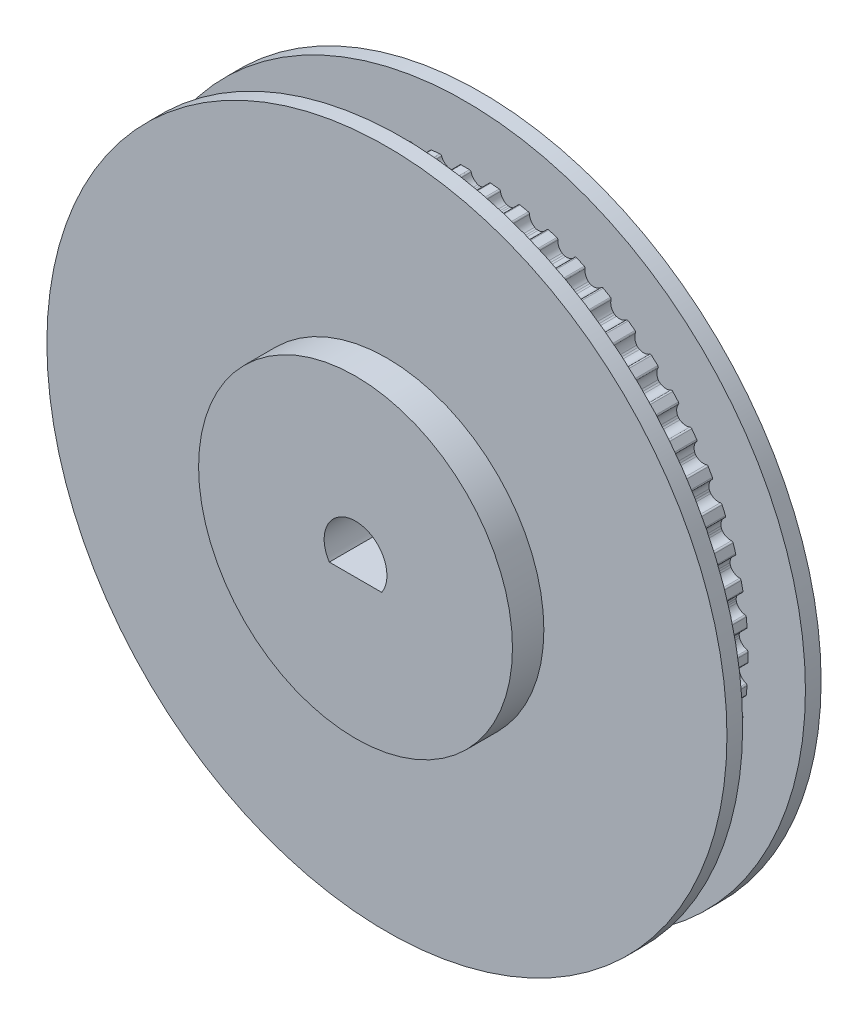
SolidWorks part; units mm, degrees
ref_plane "Front Plane" through (0, 0, 0) normal (0, 0, 1) x (1, 0, 0)
ref_plane "Top Plane" through (0, 0, 0) normal (0, 1, 0) x (1, 0, 0)
ref_plane "Right Plane" through (0, 0, 0) normal (1, 0, 0) x (0, 0, -1)
sketch "Sketch2" plane through (0, 0, 0) normal (0, 0, 1) x (1, 0, 0)
  circle A0 centre (0, 0) radius 27.695
  dimension "D1" = 55.39
extrude "Boss-Extrude1" add sketch "Sketch2" along normal mid plane 6
sketch "Sketch3" plane through (0, 0, 3) normal (0, 0, 1) x (1, 0, 0)
  line L0 (0, 0) -> (0, 27.0327) construction
  line L1 (0, 27.0327) -> (0.4, 27.0327)
  line L4 (0, 0) -> (1.4605, 27.8689) construction
  line L8 (0, 27.0327) -> (0, 27.8689)
  line L9 (0, 27.8689) -> (1.4605, 27.8689)
  line L10 (2.9131, 27.7163) -> (1.4605, 27.8689)
  line L11 (2.8257, 26.8846) -> (2.4279, 26.9264)
  line L12 (2.8257, 26.8846) -> (2.9131, 27.7163)
  line L13 (5.7943, 27.2599) -> (4.3656, 27.5636)
  line L14 (2.9131, 27.7163) -> (4.3656, 27.5636)
  line L15 (2.8257, 26.8846) -> (2.9131, 27.7163)
  line L16 (2.8257, 26.8846) -> (3.2235, 26.8428)
  line L17 (5.6204, 26.442) -> (5.2292, 26.5251)
  line L18 (5.6204, 26.442) -> (5.7943, 27.2599)
  line L19 (8.612, 26.5049) -> (7.2229, 26.9563)
  line L20 (5.7943, 27.2599) -> (7.2229, 26.9563)
  line L21 (5.6204, 26.442) -> (5.7943, 27.2599)
  line L22 (5.6204, 26.442) -> (6.0117, 26.3588)
  line L23 (8.3536, 25.7096) -> (7.9731, 25.8332)
  line L24 (8.3536, 25.7096) -> (8.612, 26.5049)
  line L25 (11.3353, 25.4595) -> (10.001, 26.0536)
  line L26 (8.612, 26.5049) -> (10.001, 26.0536)
  line L27 (8.3536, 25.7096) -> (8.612, 26.5049)
  line L28 (8.3536, 25.7096) -> (8.734, 25.586)
  line L29 (10.9952, 24.6956) -> (10.6298, 24.8583)
  line L30 (10.9952, 24.6956) -> (11.3353, 25.4595)
  line L31 (13.9345, 24.1352) -> (12.6696, 24.8655)
  line L32 (11.3353, 25.4595) -> (12.6696, 24.8655)
  line L33 (10.9952, 24.6956) -> (11.3353, 25.4595)
  line L34 (10.9952, 24.6956) -> (11.3606, 24.5329)
  line L35 (13.5164, 23.411) -> (13.1699, 23.611)
  line L36 (13.5164, 23.411) -> (13.9345, 24.1352)
  line L37 (16.381, 22.5465) -> (15.1993, 23.4049)
  line L38 (13.9345, 24.1352) -> (15.1993, 23.4049)
  line L39 (13.5164, 23.411) -> (13.9345, 24.1352)
  line L40 (13.5164, 23.411) -> (13.8628, 23.211)
  line L41 (15.8894, 21.8699) -> (15.5658, 22.105)
  line L42 (15.8894, 21.8699) -> (16.381, 22.5465)
  line L43 (18.648, 20.7107) -> (17.5626, 21.688)
  line L44 (16.381, 22.5465) -> (17.5626, 21.688)
  line L45 (15.8894, 21.8699) -> (16.381, 22.5465)
  line L46 (15.8894, 21.8699) -> (16.213, 21.6348)
  line L47 (18.0884, 20.0892) -> (17.7911, 20.3569)
  line L48 (18.0884, 20.0892) -> (18.648, 20.7107)
  line L49 (20.7107, 18.648) -> (19.7334, 19.7334)
  line L50 (18.648, 20.7107) -> (19.7334, 19.7334)
  line L51 (18.0884, 20.0892) -> (18.648, 20.7107)
  line L52 (18.0884, 20.0892) -> (18.3857, 19.8216)
  line L53 (20.0892, 18.0884) -> (19.8216, 18.3857)
  line L54 (20.0892, 18.0884) -> (20.7107, 18.648)
  line L55 (22.5465, 16.381) -> (21.688, 17.5626)
  line L56 (20.7107, 18.648) -> (21.688, 17.5626)
  line L57 (20.0892, 18.0884) -> (20.7107, 18.648)
  line L58 (20.0892, 18.0884) -> (20.3569, 17.7911)
  line L59 (21.8699, 15.8894) -> (21.6348, 16.213)
  line L60 (21.8699, 15.8894) -> (22.5465, 16.381)
  line L61 (24.1352, 13.9345) -> (23.4049, 15.1993)
  line L62 (22.5465, 16.381) -> (23.4049, 15.1993)
  line L63 (21.8699, 15.8894) -> (22.5465, 16.381)
  line L64 (21.8699, 15.8894) -> (22.105, 15.5658)
  line L65 (23.411, 13.5164) -> (23.211, 13.8628)
  line L66 (23.411, 13.5164) -> (24.1352, 13.9345)
  line L67 (25.4595, 11.3353) -> (24.8655, 12.6696)
  line L68 (24.1352, 13.9345) -> (24.8655, 12.6696)
  line L69 (23.411, 13.5164) -> (24.1352, 13.9345)
  line L70 (23.411, 13.5164) -> (23.611, 13.1699)
  line L71 (24.6956, 10.9952) -> (24.5329, 11.3606)
  line L72 (24.6956, 10.9952) -> (25.4595, 11.3353)
  line L73 (26.5049, 8.612) -> (26.0536, 10.001)
  line L74 (25.4595, 11.3353) -> (26.0536, 10.001)
  line L75 (24.6956, 10.9952) -> (25.4595, 11.3353)
  line L76 (24.6956, 10.9952) -> (24.8583, 10.6298)
  line L77 (25.7096, 8.3536) -> (25.586, 8.734)
  line L78 (25.7096, 8.3536) -> (26.5049, 8.612)
  line L79 (27.2599, 5.7943) -> (26.9563, 7.2229)
  line L80 (26.5049, 8.612) -> (26.9563, 7.2229)
  line L81 (25.7096, 8.3536) -> (26.5049, 8.612)
  line L82 (25.7096, 8.3536) -> (25.8332, 7.9731)
  line L83 (26.442, 5.6204) -> (26.3588, 6.0117)
  line L84 (26.442, 5.6204) -> (27.2599, 5.7943)
  line L85 (27.7163, 2.9131) -> (27.5636, 4.3656)
  line L86 (27.2599, 5.7943) -> (27.5636, 4.3656)
  line L87 (26.442, 5.6204) -> (27.2599, 5.7943)
  line L88 (26.442, 5.6204) -> (26.5251, 5.2292)
  line L89 (26.8846, 2.8257) -> (26.8428, 3.2235)
  line L90 (26.8846, 2.8257) -> (27.7163, 2.9131)
  line L91 (27.8689, 0) -> (27.8689, 1.4605)
  line L92 (27.7163, 2.9131) -> (27.8689, 1.4605)
  line L93 (26.8846, 2.8257) -> (27.7163, 2.9131)
  line L94 (26.8846, 2.8257) -> (26.9264, 2.4279)
  line L95 (27.0327, 0) -> (27.0327, 0.4)
  line L96 (27.0327, 0) -> (27.8689, 0)
  line L97 (27.7163, -2.9131) -> (27.8689, -1.4605)
  line L98 (27.8689, 0) -> (27.8689, -1.4605)
  line L99 (27.0327, 0) -> (27.8689, 0)
  line L100 (27.0327, 0) -> (27.0327, -0.4)
  line L101 (26.8846, -2.8257) -> (26.9264, -2.4279)
  line L102 (26.8846, -2.8257) -> (27.7163, -2.9131)
  line L103 (27.2599, -5.7943) -> (27.5636, -4.3656)
  line L104 (27.7163, -2.9131) -> (27.5636, -4.3656)
  line L105 (26.8846, -2.8257) -> (27.7163, -2.9131)
  line L106 (26.8846, -2.8257) -> (26.8428, -3.2235)
  line L107 (26.442, -5.6204) -> (26.5251, -5.2292)
  line L108 (26.442, -5.6204) -> (27.2599, -5.7943)
  line L109 (26.5049, -8.612) -> (26.9563, -7.2229)
  line L110 (27.2599, -5.7943) -> (26.9563, -7.2229)
  line L111 (26.442, -5.6204) -> (27.2599, -5.7943)
  line L112 (26.442, -5.6204) -> (26.3588, -6.0117)
  line L113 (25.7096, -8.3536) -> (25.8332, -7.9731)
  line L114 (25.7096, -8.3536) -> (26.5049, -8.612)
  line L115 (25.4595, -11.3353) -> (26.0536, -10.001)
  line L116 (26.5049, -8.612) -> (26.0536, -10.001)
  line L117 (25.7096, -8.3536) -> (26.5049, -8.612)
  line L118 (25.7096, -8.3536) -> (25.586, -8.734)
  line L119 (24.6956, -10.9952) -> (24.8583, -10.6298)
  line L120 (24.6956, -10.9952) -> (25.4595, -11.3353)
  line L121 (24.1352, -13.9345) -> (24.8655, -12.6696)
  line L122 (25.4595, -11.3353) -> (24.8655, -12.6696)
  line L123 (24.6956, -10.9952) -> (25.4595, -11.3353)
  line L124 (24.6956, -10.9952) -> (24.5329, -11.3606)
  line L125 (23.411, -13.5164) -> (23.611, -13.1699)
  line L126 (23.411, -13.5164) -> (24.1352, -13.9345)
  line L127 (22.5465, -16.381) -> (23.4049, -15.1993)
  line L128 (24.1352, -13.9345) -> (23.4049, -15.1993)
  line L129 (23.411, -13.5164) -> (24.1352, -13.9345)
  line L130 (23.411, -13.5164) -> (23.211, -13.8628)
  line L131 (21.8699, -15.8894) -> (22.105, -15.5658)
  line L132 (21.8699, -15.8894) -> (22.5465, -16.381)
  line L133 (20.7107, -18.648) -> (21.688, -17.5626)
  line L134 (22.5465, -16.381) -> (21.688, -17.5626)
  line L135 (21.8699, -15.8894) -> (22.5465, -16.381)
  line L136 (21.8699, -15.8894) -> (21.6348, -16.213)
  line L137 (20.0892, -18.0884) -> (20.3569, -17.7911)
  line L138 (20.0892, -18.0884) -> (20.7107, -18.648)
  line L139 (18.648, -20.7107) -> (19.7334, -19.7334)
  line L140 (20.7107, -18.648) -> (19.7334, -19.7334)
  line L141 (20.0892, -18.0884) -> (20.7107, -18.648)
  line L142 (20.0892, -18.0884) -> (19.8216, -18.3857)
  line L143 (18.0884, -20.0892) -> (18.3857, -19.8216)
  line L144 (18.0884, -20.0892) -> (18.648, -20.7107)
  line L145 (16.381, -22.5465) -> (17.5626, -21.688)
  line L146 (18.648, -20.7107) -> (17.5626, -21.688)
  line L147 (18.0884, -20.0892) -> (18.648, -20.7107)
  line L148 (18.0884, -20.0892) -> (17.7911, -20.3569)
  line L149 (15.8894, -21.8699) -> (16.213, -21.6348)
  line L150 (15.8894, -21.8699) -> (16.381, -22.5465)
  line L151 (13.9345, -24.1352) -> (15.1993, -23.4049)
  line L152 (16.381, -22.5465) -> (15.1993, -23.4049)
  line L153 (15.8894, -21.8699) -> (16.381, -22.5465)
  line L154 (15.8894, -21.8699) -> (15.5658, -22.105)
  line L155 (13.5164, -23.411) -> (13.8628, -23.211)
  line L156 (13.5164, -23.411) -> (13.9345, -24.1352)
  line L157 (11.3353, -25.4595) -> (12.6696, -24.8655)
  line L158 (13.9345, -24.1352) -> (12.6696, -24.8655)
  line L159 (13.5164, -23.411) -> (13.9345, -24.1352)
  line L160 (13.5164, -23.411) -> (13.1699, -23.611)
  line L161 (10.9952, -24.6956) -> (11.3606, -24.5329)
  line L162 (10.9952, -24.6956) -> (11.3353, -25.4595)
  line L163 (8.612, -26.5049) -> (10.001, -26.0536)
  line L164 (11.3353, -25.4595) -> (10.001, -26.0536)
  line L165 (10.9952, -24.6956) -> (11.3353, -25.4595)
  line L166 (10.9952, -24.6956) -> (10.6298, -24.8583)
  line L167 (8.3536, -25.7096) -> (8.734, -25.586)
  line L168 (8.3536, -25.7096) -> (8.612, -26.5049)
  line L169 (5.7943, -27.2599) -> (7.2229, -26.9563)
  line L170 (8.612, -26.5049) -> (7.2229, -26.9563)
  line L171 (8.3536, -25.7096) -> (8.612, -26.5049)
  line L172 (8.3536, -25.7096) -> (7.9731, -25.8332)
  line L173 (5.6204, -26.442) -> (6.0117, -26.3588)
  line L174 (5.6204, -26.442) -> (5.7943, -27.2599)
  line L175 (2.9131, -27.7163) -> (4.3656, -27.5636)
  line L176 (5.7943, -27.2599) -> (4.3656, -27.5636)
  line L177 (5.6204, -26.442) -> (5.7943, -27.2599)
  line L178 (5.6204, -26.442) -> (5.2292, -26.5251)
  line L179 (2.8257, -26.8846) -> (3.2235, -26.8428)
  line L180 (2.8257, -26.8846) -> (2.9131, -27.7163)
  line L181 (0, -27.8689) -> (1.4605, -27.8689)
  line L182 (2.9131, -27.7163) -> (1.4605, -27.8689)
  line L183 (2.8257, -26.8846) -> (2.9131, -27.7163)
  line L184 (2.8257, -26.8846) -> (2.4279, -26.9264)
  line L185 (0, -27.0327) -> (0.4, -27.0327)
  line L186 (0, -27.0327) -> (0, -27.8689)
  line L187 (-2.9131, -27.7163) -> (-1.4605, -27.8689)
  line L188 (0, -27.8689) -> (-1.4605, -27.8689)
  line L189 (0, -27.0327) -> (0, -27.8689)
  line L190 (0, -27.0327) -> (-0.4, -27.0327)
  line L191 (-2.8257, -26.8846) -> (-2.4279, -26.9264)
  line L192 (-2.8257, -26.8846) -> (-2.9131, -27.7163)
  line L193 (-5.7943, -27.2599) -> (-4.3656, -27.5636)
  line L194 (-2.9131, -27.7163) -> (-4.3656, -27.5636)
  line L195 (-2.8257, -26.8846) -> (-2.9131, -27.7163)
  line L196 (-2.8257, -26.8846) -> (-3.2235, -26.8428)
  line L197 (-5.6204, -26.442) -> (-5.2292, -26.5251)
  line L198 (-5.6204, -26.442) -> (-5.7943, -27.2599)
  line L199 (-8.612, -26.5049) -> (-7.2229, -26.9563)
  line L200 (-5.7943, -27.2599) -> (-7.2229, -26.9563)
  line L201 (-5.6204, -26.442) -> (-5.7943, -27.2599)
  line L202 (-5.6204, -26.442) -> (-6.0117, -26.3588)
  line L203 (-8.3536, -25.7096) -> (-7.9731, -25.8332)
  line L204 (-8.3536, -25.7096) -> (-8.612, -26.5049)
  line L205 (-11.3353, -25.4595) -> (-10.001, -26.0536)
  line L206 (-8.612, -26.5049) -> (-10.001, -26.0536)
  line L207 (-8.3536, -25.7096) -> (-8.612, -26.5049)
  line L208 (-8.3536, -25.7096) -> (-8.734, -25.586)
  line L209 (-10.9952, -24.6956) -> (-10.6298, -24.8583)
  line L210 (-10.9952, -24.6956) -> (-11.3353, -25.4595)
  line L211 (-13.9345, -24.1352) -> (-12.6696, -24.8655)
  line L212 (-11.3353, -25.4595) -> (-12.6696, -24.8655)
  line L213 (-10.9952, -24.6956) -> (-11.3353, -25.4595)
  line L214 (-10.9952, -24.6956) -> (-11.3606, -24.5329)
  line L215 (-13.5164, -23.411) -> (-13.1699, -23.611)
  line L216 (-13.5164, -23.411) -> (-13.9345, -24.1352)
  line L217 (-16.381, -22.5465) -> (-15.1993, -23.4049)
  line L218 (-13.9345, -24.1352) -> (-15.1993, -23.4049)
  line L219 (-13.5164, -23.411) -> (-13.9345, -24.1352)
  line L220 (-13.5164, -23.411) -> (-13.8628, -23.211)
  line L221 (-15.8894, -21.8699) -> (-15.5658, -22.105)
  line L222 (-15.8894, -21.8699) -> (-16.381, -22.5465)
  line L223 (-18.648, -20.7107) -> (-17.5626, -21.688)
  line L224 (-16.381, -22.5465) -> (-17.5626, -21.688)
  line L225 (-15.8894, -21.8699) -> (-16.381, -22.5465)
  line L226 (-15.8894, -21.8699) -> (-16.213, -21.6348)
  line L227 (-18.0884, -20.0892) -> (-17.7911, -20.3569)
  line L228 (-18.0884, -20.0892) -> (-18.648, -20.7107)
  line L229 (-20.7107, -18.648) -> (-19.7334, -19.7334)
  line L230 (-18.648, -20.7107) -> (-19.7334, -19.7334)
  line L231 (-18.0884, -20.0892) -> (-18.648, -20.7107)
  line L232 (-18.0884, -20.0892) -> (-18.3857, -19.8216)
  line L233 (-20.0892, -18.0884) -> (-19.8216, -18.3857)
  line L234 (-20.0892, -18.0884) -> (-20.7107, -18.648)
  line L235 (-22.5465, -16.381) -> (-21.688, -17.5626)
  line L236 (-20.7107, -18.648) -> (-21.688, -17.5626)
  line L237 (-20.0892, -18.0884) -> (-20.7107, -18.648)
  line L238 (-20.0892, -18.0884) -> (-20.3569, -17.7911)
  line L239 (-21.8699, -15.8894) -> (-21.6348, -16.213)
  line L240 (-21.8699, -15.8894) -> (-22.5465, -16.381)
  line L241 (-24.1352, -13.9345) -> (-23.4049, -15.1993)
  line L242 (-22.5465, -16.381) -> (-23.4049, -15.1993)
  line L243 (-21.8699, -15.8894) -> (-22.5465, -16.381)
  line L244 (-21.8699, -15.8894) -> (-22.105, -15.5658)
  line L245 (-23.411, -13.5164) -> (-23.211, -13.8628)
  line L246 (-23.411, -13.5164) -> (-24.1352, -13.9345)
  line L247 (-25.4595, -11.3353) -> (-24.8655, -12.6696)
  line L248 (-24.1352, -13.9345) -> (-24.8655, -12.6696)
  line L249 (-23.411, -13.5164) -> (-24.1352, -13.9345)
  line L250 (-23.411, -13.5164) -> (-23.611, -13.1699)
  line L251 (-24.6956, -10.9952) -> (-24.5329, -11.3606)
  line L252 (-24.6956, -10.9952) -> (-25.4595, -11.3353)
  line L253 (-26.5049, -8.612) -> (-26.0536, -10.001)
  line L254 (-25.4595, -11.3353) -> (-26.0536, -10.001)
  line L255 (-24.6956, -10.9952) -> (-25.4595, -11.3353)
  line L256 (-24.6956, -10.9952) -> (-24.8583, -10.6298)
  line L257 (-25.7096, -8.3536) -> (-25.586, -8.734)
  line L258 (-25.7096, -8.3536) -> (-26.5049, -8.612)
  line L259 (-27.2599, -5.7943) -> (-26.9563, -7.2229)
  line L260 (-26.5049, -8.612) -> (-26.9563, -7.2229)
  line L261 (-25.7096, -8.3536) -> (-26.5049, -8.612)
  line L262 (-25.7096, -8.3536) -> (-25.8332, -7.9731)
  line L263 (-26.442, -5.6204) -> (-26.3588, -6.0117)
  line L264 (-26.442, -5.6204) -> (-27.2599, -5.7943)
  line L265 (-27.7163, -2.9131) -> (-27.5636, -4.3656)
  line L266 (-27.2599, -5.7943) -> (-27.5636, -4.3656)
  line L267 (-26.442, -5.6204) -> (-27.2599, -5.7943)
  line L268 (-26.442, -5.6204) -> (-26.5251, -5.2292)
  line L269 (-26.8846, -2.8257) -> (-26.8428, -3.2235)
  line L270 (-26.8846, -2.8257) -> (-27.7163, -2.9131)
  line L271 (-27.8689, 0) -> (-27.8689, -1.4605)
  line L272 (-27.7163, -2.9131) -> (-27.8689, -1.4605)
  line L273 (-26.8846, -2.8257) -> (-27.7163, -2.9131)
  line L274 (-26.8846, -2.8257) -> (-26.9264, -2.4279)
  line L275 (-27.0327, 0) -> (-27.0327, -0.4)
  line L276 (-27.0327, 0) -> (-27.8689, 0)
  line L277 (-27.7163, 2.9131) -> (-27.8689, 1.4605)
  line L278 (-27.8689, 0) -> (-27.8689, 1.4605)
  line L279 (-27.0327, 0) -> (-27.8689, 0)
  line L280 (-27.0327, 0) -> (-27.0327, 0.4)
  line L281 (-26.8846, 2.8257) -> (-26.9264, 2.4279)
  line L282 (-26.8846, 2.8257) -> (-27.7163, 2.9131)
  line L283 (-27.2599, 5.7943) -> (-27.5636, 4.3656)
  line L284 (-27.7163, 2.9131) -> (-27.5636, 4.3656)
  line L285 (-26.8846, 2.8257) -> (-27.7163, 2.9131)
  line L286 (-26.8846, 2.8257) -> (-26.8428, 3.2235)
  line L287 (-26.442, 5.6204) -> (-26.5251, 5.2292)
  line L288 (-26.442, 5.6204) -> (-27.2599, 5.7943)
  line L289 (-26.5049, 8.612) -> (-26.9563, 7.2229)
  line L290 (-27.2599, 5.7943) -> (-26.9563, 7.2229)
  line L291 (-26.442, 5.6204) -> (-27.2599, 5.7943)
  line L292 (-26.442, 5.6204) -> (-26.3588, 6.0117)
  line L293 (-25.7096, 8.3536) -> (-25.8332, 7.9731)
  line L294 (-25.7096, 8.3536) -> (-26.5049, 8.612)
  line L295 (-25.4595, 11.3353) -> (-26.0536, 10.001)
  line L296 (-26.5049, 8.612) -> (-26.0536, 10.001)
  line L297 (-25.7096, 8.3536) -> (-26.5049, 8.612)
  line L298 (-25.7096, 8.3536) -> (-25.586, 8.734)
  line L299 (-24.6956, 10.9952) -> (-24.8583, 10.6298)
  line L300 (-24.6956, 10.9952) -> (-25.4595, 11.3353)
  line L301 (-24.1352, 13.9345) -> (-24.8655, 12.6696)
  line L302 (-25.4595, 11.3353) -> (-24.8655, 12.6696)
  line L303 (-24.6956, 10.9952) -> (-25.4595, 11.3353)
  line L304 (-24.6956, 10.9952) -> (-24.5329, 11.3606)
  line L305 (-23.411, 13.5164) -> (-23.611, 13.1699)
  line L306 (-23.411, 13.5164) -> (-24.1352, 13.9345)
  line L307 (-22.5465, 16.381) -> (-23.4049, 15.1993)
  line L308 (-24.1352, 13.9345) -> (-23.4049, 15.1993)
  line L309 (-23.411, 13.5164) -> (-24.1352, 13.9345)
  line L310 (-23.411, 13.5164) -> (-23.211, 13.8628)
  line L311 (-21.8699, 15.8894) -> (-22.105, 15.5658)
  line L312 (-21.8699, 15.8894) -> (-22.5465, 16.381)
  line L313 (-20.7107, 18.648) -> (-21.688, 17.5626)
  line L314 (-22.5465, 16.381) -> (-21.688, 17.5626)
  line L315 (-21.8699, 15.8894) -> (-22.5465, 16.381)
  line L316 (-21.8699, 15.8894) -> (-21.6348, 16.213)
  line L317 (-20.0892, 18.0884) -> (-20.3569, 17.7911)
  line L318 (-20.0892, 18.0884) -> (-20.7107, 18.648)
  line L319 (-18.648, 20.7107) -> (-19.7334, 19.7334)
  line L320 (-20.7107, 18.648) -> (-19.7334, 19.7334)
  line L321 (-20.0892, 18.0884) -> (-20.7107, 18.648)
  line L322 (-20.0892, 18.0884) -> (-19.8216, 18.3857)
  line L323 (-18.0884, 20.0892) -> (-18.3857, 19.8216)
  line L324 (-18.0884, 20.0892) -> (-18.648, 20.7107)
  line L325 (-16.381, 22.5465) -> (-17.5626, 21.688)
  line L326 (-18.648, 20.7107) -> (-17.5626, 21.688)
  line L327 (-18.0884, 20.0892) -> (-18.648, 20.7107)
  line L328 (-18.0884, 20.0892) -> (-17.7911, 20.3569)
  line L329 (-15.8894, 21.8699) -> (-16.213, 21.6348)
  line L330 (-15.8894, 21.8699) -> (-16.381, 22.5465)
  line L331 (-13.9345, 24.1352) -> (-15.1993, 23.4049)
  line L332 (-16.381, 22.5465) -> (-15.1993, 23.4049)
  line L333 (-15.8894, 21.8699) -> (-16.381, 22.5465)
  line L334 (-15.8894, 21.8699) -> (-15.5658, 22.105)
  line L335 (-13.5164, 23.411) -> (-13.8628, 23.211)
  line L336 (-13.5164, 23.411) -> (-13.9345, 24.1352)
  line L337 (-11.3353, 25.4595) -> (-12.6696, 24.8655)
  line L338 (-13.9345, 24.1352) -> (-12.6696, 24.8655)
  line L339 (-13.5164, 23.411) -> (-13.9345, 24.1352)
  line L340 (-13.5164, 23.411) -> (-13.1699, 23.611)
  line L341 (-10.9952, 24.6956) -> (-11.3606, 24.5329)
  line L342 (-10.9952, 24.6956) -> (-11.3353, 25.4595)
  line L343 (-8.612, 26.5049) -> (-10.001, 26.0536)
  line L344 (-11.3353, 25.4595) -> (-10.001, 26.0536)
  line L345 (-10.9952, 24.6956) -> (-11.3353, 25.4595)
  line L346 (-10.9952, 24.6956) -> (-10.6298, 24.8583)
  line L347 (-8.3536, 25.7096) -> (-8.734, 25.586)
  line L348 (-8.3536, 25.7096) -> (-8.612, 26.5049)
  line L349 (-5.7943, 27.2599) -> (-7.2229, 26.9563)
  line L350 (-8.612, 26.5049) -> (-7.2229, 26.9563)
  line L351 (-8.3536, 25.7096) -> (-8.612, 26.5049)
  line L352 (-8.3536, 25.7096) -> (-7.9731, 25.8332)
  line L353 (-5.6204, 26.442) -> (-6.0117, 26.3588)
  line L354 (-5.6204, 26.442) -> (-5.7943, 27.2599)
  line L355 (-2.9131, 27.7163) -> (-4.3656, 27.5636)
  line L356 (-5.7943, 27.2599) -> (-4.3656, 27.5636)
  line L357 (-5.6204, 26.442) -> (-5.7943, 27.2599)
  line L358 (-5.6204, 26.442) -> (-5.2292, 26.5251)
  line L359 (-2.8257, 26.8846) -> (-3.2235, 26.8428)
  line L360 (-2.8257, 26.8846) -> (-2.9131, 27.7163)
  line L361 (0, 27.8689) -> (-1.4605, 27.8689)
  line L362 (-2.9131, 27.7163) -> (-1.4605, 27.8689)
  line L363 (-2.8257, 26.8846) -> (-2.9131, 27.7163)
  line L364 (-2.8257, 26.8846) -> (-2.4279, 26.9264)
  line L365 (0, 27.0327) -> (-0.4, 27.0327)
  line L366 (0, 27.0327) -> (0, 27.8689)
  arc A0 (0.4, 27.0327) -> (0.5459, 26.9176) centre (0.4, 26.8827) cw
  arc A1 (0.5459, 26.9176) -> (1.1992, 26.2023) centre (1.5185, 27.1499) ccw
  arc A2 (1.1992, 26.2023) -> (1.3717, 26.1737) centre (1.3749, 26.7287) ccw
  arc A3 (3.2235, 26.8428) -> (3.3566, 26.713) centre (3.2078, 26.6936) cw
  arc A4 (1.5463, 26.1841) -> (1.3717, 26.1737) centre (1.4265, 26.726) cw
  arc A5 (2.2707, 26.8272) -> (1.5463, 26.1841) centre (1.3277, 27.1599) cw
  arc A6 (2.4279, 26.9264) -> (2.2707, 26.8272) centre (2.4122, 26.7772) ccw
  arc A7 (3.3566, 26.713) -> (3.9315, 25.9334) centre (4.3481, 26.8425) ccw
  arc A8 (3.9315, 25.9334) -> (4.1001, 25.887) centre (4.1613, 26.4386) ccw
  arc A9 (4.2748, 25.879) -> (4.1001, 25.887) centre (4.2123, 26.4305) cw
  arc A10 (5.0625, 26.4428) -> (4.2748, 25.879) centre (4.1595, 26.8724) cw
  arc A11 (5.2292, 26.5251) -> (5.0625, 26.4428) centre (5.198, 26.3784) ccw
  arc A12 (6.0117, 26.3588) -> (6.1304, 26.2158) centre (5.9805, 26.2121) cw
  arc A13 (6.1304, 26.2158) -> (6.6207, 25.3804) centre (7.1301, 26.2409) ccw
  arc A14 (6.6207, 25.3804) -> (6.7836, 25.3166) centre (6.9021, 25.8588) ccw
  arc A15 (6.9565, 25.2904) -> (6.7836, 25.3166) centre (6.952, 25.8454) cw
  arc A16 (7.7988, 25.7688) -> (6.9565, 25.2904) centre (6.9456, 26.2904) cw
  arc A17 (7.9731, 25.8332) -> (7.7988, 25.7688) centre (7.9268, 25.6906) ccw
  arc A18 (8.734, 25.586) -> (8.8372, 25.4314) centre (8.6876, 25.4434) cw
  arc A19 (8.8372, 25.4314) -> (9.2374, 24.5493) centre (9.834, 25.3519) ccw
  arc A20 (9.2374, 24.5493) -> (9.3927, 24.4688) centre (9.5673, 24.9957) ccw
  arc A21 (9.562, 24.4247) -> (9.3927, 24.4688) centre (9.6155, 24.9771) cw
  arc A22 (10.4497, 24.8124) -> (9.562, 24.4247) centre (9.6556, 25.4203) cw
  arc A23 (10.6298, 24.8583) -> (10.4497, 24.8124) centre (10.5688, 24.7213) ccw
  arc A24 (11.3606, 24.5329) -> (11.4471, 24.3684) centre (11.2996, 24.3959) cw
  arc A25 (11.4471, 24.3684) -> (11.7529, 23.4493) centre (12.4301, 24.1851) ccw
  arc A26 (11.7529, 23.4493) -> (11.8989, 23.353) centre (12.1276, 23.8587) ccw
  arc A27 (12.0627, 23.2914) -> (11.8989, 23.353) centre (12.1736, 23.8352) cw
  arc A28 (12.986, 23.5842) -> (12.0627, 23.2914) centre (12.2599, 24.2718) cw
  arc A29 (13.1699, 23.611) -> (12.986, 23.5842) centre (13.0949, 23.4811) ccw
  arc A30 (13.8628, 23.211) -> (13.9315, 23.0383) centre (13.7878, 23.0811) cw
  arc A31 (13.9315, 23.0383) -> (14.1396, 22.0923) centre (14.89, 22.7533) ccw
  arc A32 (14.1396, 22.0923) -> (14.2748, 21.9813) centre (14.5551, 22.4603) ccw
  arc A33 (14.4312, 21.903) -> (14.2748, 21.9813) centre (14.5984, 22.4322) cw
  arc A34 (15.3801, 22.0976) -> (14.4312, 21.903) centre (14.7298, 22.8573) cw
  arc A35 (15.5658, 22.105) -> (15.3801, 22.0976) centre (15.4776, 21.9837) ccw
  arc A36 (16.213, 21.6348) -> (16.2634, 21.4559) centre (16.1249, 21.5134) cw
  arc A37 (16.2634, 21.4559) -> (16.3715, 20.4933) centre (17.1868, 21.0722) ccw
  arc A38 (16.3715, 20.4933) -> (16.4943, 20.3687) centre (16.8231, 20.8158) ccw
  arc A39 (16.6416, 20.2745) -> (16.4943, 20.3687) centre (16.8632, 20.7833) cw
  arc A40 (17.6057, 20.3689) -> (16.6416, 20.2745) centre (17.0384, 21.1924) cw
  arc A41 (17.7911, 20.3569) -> (17.6057, 20.3689) centre (17.6908, 20.2454) ccw
  arc A42 (18.3857, 19.8216) -> (18.417, 19.6384) centre (18.2853, 19.7101) cw
  arc A43 (18.417, 19.6384) -> (18.4239, 18.6697) centre (19.2953, 19.1602) ccw
  arc A44 (18.4239, 18.6697) -> (18.533, 18.533) centre (18.9068, 18.9433) ccw
  arc A45 (18.6697, 18.4239) -> (18.533, 18.533) centre (18.9433, 18.9068) cw
  arc A46 (19.6384, 18.417) -> (18.6697, 18.4239) centre (19.1602, 19.2953) cw
  arc A47 (19.8216, 18.3857) -> (19.6384, 18.417) centre (19.7101, 18.2853) ccw
  arc A48 (20.3569, 17.7911) -> (20.3689, 17.6057) centre (20.2454, 17.6908) cw
  arc A49 (20.3689, 17.6057) -> (20.2745, 16.6416) centre (21.1924, 17.0384) ccw
  arc A50 (20.2745, 16.6416) -> (20.3687, 16.4943) centre (20.7833, 16.8632) ccw
  arc A51 (20.4933, 16.3715) -> (20.3687, 16.4943) centre (20.8158, 16.8231) cw
  arc A52 (21.4559, 16.2634) -> (20.4933, 16.3715) centre (21.0722, 17.1868) cw
  arc A53 (21.6348, 16.213) -> (21.4559, 16.2634) centre (21.5134, 16.1249) ccw
  arc A54 (22.105, 15.5658) -> (22.0976, 15.3801) centre (21.9837, 15.4776) cw
  arc A55 (22.0976, 15.3801) -> (21.903, 14.4312) centre (22.8573, 14.7298) ccw
  arc A56 (21.903, 14.4312) -> (21.9813, 14.2748) centre (22.4322, 14.5984) ccw
  arc A57 (22.0923, 14.1396) -> (21.9813, 14.2748) centre (22.4603, 14.5551) cw
  arc A58 (23.0383, 13.9315) -> (22.0923, 14.1396) centre (22.7533, 14.89) cw
  arc A59 (23.211, 13.8628) -> (23.0383, 13.9315) centre (23.0811, 13.7878) ccw
  arc A60 (23.611, 13.1699) -> (23.5842, 12.986) centre (23.4811, 13.0949) cw
  arc A61 (23.5842, 12.986) -> (23.2914, 12.0627) centre (24.2718, 12.2599) ccw
  arc A62 (23.2914, 12.0627) -> (23.353, 11.8989) centre (23.8352, 12.1736) ccw
  arc A63 (23.4493, 11.7529) -> (23.353, 11.8989) centre (23.8587, 12.1276) cw
  arc A64 (24.3684, 11.4471) -> (23.4493, 11.7529) centre (24.1851, 12.4301) cw
  arc A65 (24.5329, 11.3606) -> (24.3684, 11.4471) centre (24.3959, 11.2996) ccw
  arc A66 (24.8583, 10.6298) -> (24.8124, 10.4497) centre (24.7213, 10.5688) cw
  arc A67 (24.8124, 10.4497) -> (24.4247, 9.562) centre (25.4203, 9.6556) ccw
  arc A68 (24.4247, 9.562) -> (24.4688, 9.3927) centre (24.9771, 9.6155) ccw
  arc A69 (24.5493, 9.2374) -> (24.4688, 9.3927) centre (24.9957, 9.5673) cw
  arc A70 (25.4314, 8.8372) -> (24.5493, 9.2374) centre (25.3519, 9.834) cw
  arc A71 (25.586, 8.734) -> (25.4314, 8.8372) centre (25.4434, 8.6876) ccw
  arc A72 (25.8332, 7.9731) -> (25.7688, 7.7988) centre (25.6906, 7.9268) cw
  arc A73 (25.7688, 7.7988) -> (25.2904, 6.9565) centre (26.2904, 6.9456) ccw
  arc A74 (25.2904, 6.9565) -> (25.3166, 6.7836) centre (25.8454, 6.952) ccw
  arc A75 (25.3804, 6.6207) -> (25.3166, 6.7836) centre (25.8588, 6.9021) cw
  arc A76 (26.2158, 6.1304) -> (25.3804, 6.6207) centre (26.2409, 7.1301) cw
  arc A77 (26.3588, 6.0117) -> (26.2158, 6.1304) centre (26.2121, 5.9805) ccw
  arc A78 (26.5251, 5.2292) -> (26.4428, 5.0625) centre (26.3784, 5.198) cw
  arc A79 (26.4428, 5.0625) -> (25.879, 4.2748) centre (26.8724, 4.1595) ccw
  arc A80 (25.879, 4.2748) -> (25.887, 4.1001) centre (26.4305, 4.2123) ccw
  arc A81 (25.9334, 3.9315) -> (25.887, 4.1001) centre (26.4386, 4.1613) cw
  arc A82 (26.713, 3.3566) -> (25.9334, 3.9315) centre (26.8425, 4.3481) cw
  arc A83 (26.8428, 3.2235) -> (26.713, 3.3566) centre (26.6936, 3.2078) ccw
  arc A84 (26.9264, 2.4279) -> (26.8272, 2.2707) centre (26.7772, 2.4122) cw
  arc A85 (26.8272, 2.2707) -> (26.1841, 1.5463) centre (27.1599, 1.3277) ccw
  arc A86 (26.1841, 1.5463) -> (26.1737, 1.3717) centre (26.726, 1.4265) ccw
  arc A87 (26.2023, 1.1992) -> (26.1737, 1.3717) centre (26.7287, 1.3749) cw
  arc A88 (26.9176, 0.5459) -> (26.2023, 1.1992) centre (27.1499, 1.5185) cw
  arc A89 (27.0327, 0.4) -> (26.9176, 0.5459) centre (26.8827, 0.4) ccw
  arc A90 (27.0327, -0.4) -> (26.9176, -0.5459) centre (26.8827, -0.4) cw
  arc A91 (26.9176, -0.5459) -> (26.2023, -1.1992) centre (27.1499, -1.5185) ccw
  arc A92 (26.2023, -1.1992) -> (26.1737, -1.3717) centre (26.7287, -1.3749) ccw
  arc A93 (26.1841, -1.5463) -> (26.1737, -1.3717) centre (26.726, -1.4265) cw
  arc A94 (26.8272, -2.2707) -> (26.1841, -1.5463) centre (27.1599, -1.3277) cw
  arc A95 (26.9264, -2.4279) -> (26.8272, -2.2707) centre (26.7772, -2.4122) ccw
  arc A96 (26.8428, -3.2235) -> (26.713, -3.3566) centre (26.6936, -3.2078) cw
  arc A97 (26.713, -3.3566) -> (25.9334, -3.9315) centre (26.8425, -4.3481) ccw
  arc A98 (25.9334, -3.9315) -> (25.887, -4.1001) centre (26.4386, -4.1613) ccw
  arc A99 (25.879, -4.2748) -> (25.887, -4.1001) centre (26.4305, -4.2123) cw
  arc A100 (26.4428, -5.0625) -> (25.879, -4.2748) centre (26.8724, -4.1595) cw
  arc A101 (26.5251, -5.2292) -> (26.4428, -5.0625) centre (26.3784, -5.198) ccw
  arc A102 (26.3588, -6.0117) -> (26.2158, -6.1304) centre (26.2121, -5.9805) cw
  arc A103 (26.2158, -6.1304) -> (25.3804, -6.6207) centre (26.2409, -7.1301) ccw
  arc A104 (25.3804, -6.6207) -> (25.3166, -6.7836) centre (25.8588, -6.9021) ccw
  arc A105 (25.2904, -6.9565) -> (25.3166, -6.7836) centre (25.8454, -6.952) cw
  arc A106 (25.7688, -7.7988) -> (25.2904, -6.9565) centre (26.2904, -6.9456) cw
  arc A107 (25.8332, -7.9731) -> (25.7688, -7.7988) centre (25.6906, -7.9268) ccw
  arc A108 (25.586, -8.734) -> (25.4314, -8.8372) centre (25.4434, -8.6876) cw
  arc A109 (25.4314, -8.8372) -> (24.5493, -9.2374) centre (25.3519, -9.834) ccw
  arc A110 (24.5493, -9.2374) -> (24.4688, -9.3927) centre (24.9957, -9.5673) ccw
  arc A111 (24.4247, -9.562) -> (24.4688, -9.3927) centre (24.9771, -9.6155) cw
  arc A112 (24.8124, -10.4497) -> (24.4247, -9.562) centre (25.4203, -9.6556) cw
  arc A113 (24.8583, -10.6298) -> (24.8124, -10.4497) centre (24.7213, -10.5688) ccw
  arc A114 (24.5329, -11.3606) -> (24.3684, -11.4471) centre (24.3959, -11.2996) cw
  arc A115 (24.3684, -11.4471) -> (23.4493, -11.7529) centre (24.1851, -12.4301) ccw
  arc A116 (23.4493, -11.7529) -> (23.353, -11.8989) centre (23.8587, -12.1276) ccw
  arc A117 (23.2914, -12.0627) -> (23.353, -11.8989) centre (23.8352, -12.1736) cw
  arc A118 (23.5842, -12.986) -> (23.2914, -12.0627) centre (24.2718, -12.2599) cw
  arc A119 (23.611, -13.1699) -> (23.5842, -12.986) centre (23.4811, -13.0949) ccw
  arc A120 (23.211, -13.8628) -> (23.0383, -13.9315) centre (23.0811, -13.7878) cw
  arc A121 (23.0383, -13.9315) -> (22.0923, -14.1396) centre (22.7533, -14.89) ccw
  arc A122 (22.0923, -14.1396) -> (21.9813, -14.2748) centre (22.4603, -14.5551) ccw
  arc A123 (21.903, -14.4312) -> (21.9813, -14.2748) centre (22.4322, -14.5984) cw
  arc A124 (22.0976, -15.3801) -> (21.903, -14.4312) centre (22.8573, -14.7298) cw
  arc A125 (22.105, -15.5658) -> (22.0976, -15.3801) centre (21.9837, -15.4776) ccw
  arc A126 (21.6348, -16.213) -> (21.4559, -16.2634) centre (21.5134, -16.1249) cw
  arc A127 (21.4559, -16.2634) -> (20.4933, -16.3715) centre (21.0722, -17.1868) ccw
  arc A128 (20.4933, -16.3715) -> (20.3687, -16.4943) centre (20.8158, -16.8231) ccw
  arc A129 (20.2745, -16.6416) -> (20.3687, -16.4943) centre (20.7833, -16.8632) cw
  arc A130 (20.3689, -17.6057) -> (20.2745, -16.6416) centre (21.1924, -17.0384) cw
  arc A131 (20.3569, -17.7911) -> (20.3689, -17.6057) centre (20.2454, -17.6908) ccw
  arc A132 (19.8216, -18.3857) -> (19.6384, -18.417) centre (19.7101, -18.2853) cw
  arc A133 (19.6384, -18.417) -> (18.6697, -18.4239) centre (19.1602, -19.2953) ccw
  arc A134 (18.6697, -18.4239) -> (18.533, -18.533) centre (18.9433, -18.9068) ccw
  arc A135 (18.4239, -18.6697) -> (18.533, -18.533) centre (18.9068, -18.9433) cw
  arc A136 (18.417, -19.6384) -> (18.4239, -18.6697) centre (19.2953, -19.1602) cw
  arc A137 (18.3857, -19.8216) -> (18.417, -19.6384) centre (18.2853, -19.7101) ccw
  arc A138 (17.7911, -20.3569) -> (17.6057, -20.3689) centre (17.6908, -20.2454) cw
  arc A139 (17.6057, -20.3689) -> (16.6416, -20.2745) centre (17.0384, -21.1924) ccw
  arc A140 (16.6416, -20.2745) -> (16.4943, -20.3687) centre (16.8632, -20.7833) ccw
  arc A141 (16.3715, -20.4933) -> (16.4943, -20.3687) centre (16.8231, -20.8158) cw
  arc A142 (16.2634, -21.4559) -> (16.3715, -20.4933) centre (17.1868, -21.0722) cw
  arc A143 (16.213, -21.6348) -> (16.2634, -21.4559) centre (16.1249, -21.5134) ccw
  arc A144 (15.5658, -22.105) -> (15.3801, -22.0976) centre (15.4776, -21.9837) cw
  arc A145 (15.3801, -22.0976) -> (14.4312, -21.903) centre (14.7298, -22.8573) ccw
  arc A146 (14.4312, -21.903) -> (14.2748, -21.9813) centre (14.5984, -22.4322) ccw
  arc A147 (14.1396, -22.0923) -> (14.2748, -21.9813) centre (14.5551, -22.4603) cw
  arc A148 (13.9315, -23.0383) -> (14.1396, -22.0923) centre (14.89, -22.7533) cw
  arc A149 (13.8628, -23.211) -> (13.9315, -23.0383) centre (13.7878, -23.0811) ccw
  arc A150 (13.1699, -23.611) -> (12.986, -23.5842) centre (13.0949, -23.4811) cw
  arc A151 (12.986, -23.5842) -> (12.0627, -23.2914) centre (12.2599, -24.2718) ccw
  arc A152 (12.0627, -23.2914) -> (11.8989, -23.353) centre (12.1736, -23.8352) ccw
  arc A153 (11.7529, -23.4493) -> (11.8989, -23.353) centre (12.1276, -23.8587) cw
  arc A154 (11.4471, -24.3684) -> (11.7529, -23.4493) centre (12.4301, -24.1851) cw
  arc A155 (11.3606, -24.5329) -> (11.4471, -24.3684) centre (11.2996, -24.3959) ccw
  arc A156 (10.6298, -24.8583) -> (10.4497, -24.8124) centre (10.5688, -24.7213) cw
  arc A157 (10.4497, -24.8124) -> (9.562, -24.4247) centre (9.6556, -25.4203) ccw
  arc A158 (9.562, -24.4247) -> (9.3927, -24.4688) centre (9.6155, -24.9771) ccw
  arc A159 (9.2374, -24.5493) -> (9.3927, -24.4688) centre (9.5673, -24.9957) cw
  arc A160 (8.8372, -25.4314) -> (9.2374, -24.5493) centre (9.834, -25.3519) cw
  arc A161 (8.734, -25.586) -> (8.8372, -25.4314) centre (8.6876, -25.4434) ccw
  arc A162 (7.9731, -25.8332) -> (7.7988, -25.7688) centre (7.9268, -25.6906) cw
  arc A163 (7.7988, -25.7688) -> (6.9565, -25.2904) centre (6.9456, -26.2904) ccw
  arc A164 (6.9565, -25.2904) -> (6.7836, -25.3166) centre (6.952, -25.8454) ccw
  arc A165 (6.6207, -25.3804) -> (6.7836, -25.3166) centre (6.9021, -25.8588) cw
  arc A166 (6.1304, -26.2158) -> (6.6207, -25.3804) centre (7.1301, -26.2409) cw
  arc A167 (6.0117, -26.3588) -> (6.1304, -26.2158) centre (5.9805, -26.2121) ccw
  arc A168 (5.2292, -26.5251) -> (5.0625, -26.4428) centre (5.198, -26.3784) cw
  arc A169 (5.0625, -26.4428) -> (4.2748, -25.879) centre (4.1595, -26.8724) ccw
  arc A170 (4.2748, -25.879) -> (4.1001, -25.887) centre (4.2123, -26.4305) ccw
  arc A171 (3.9315, -25.9334) -> (4.1001, -25.887) centre (4.1613, -26.4386) cw
  arc A172 (3.3566, -26.713) -> (3.9315, -25.9334) centre (4.3481, -26.8425) cw
  arc A173 (3.2235, -26.8428) -> (3.3566, -26.713) centre (3.2078, -26.6936) ccw
  arc A174 (2.4279, -26.9264) -> (2.2707, -26.8272) centre (2.4122, -26.7772) cw
  arc A175 (2.2707, -26.8272) -> (1.5463, -26.1841) centre (1.3277, -27.1599) ccw
  arc A176 (1.5463, -26.1841) -> (1.3717, -26.1737) centre (1.4265, -26.726) ccw
  arc A177 (1.1992, -26.2023) -> (1.3717, -26.1737) centre (1.3749, -26.7287) cw
  arc A178 (0.5459, -26.9176) -> (1.1992, -26.2023) centre (1.5185, -27.1499) cw
  arc A179 (0.4, -27.0327) -> (0.5459, -26.9176) centre (0.4, -26.8827) ccw
  arc A180 (-0.4, -27.0327) -> (-0.5459, -26.9176) centre (-0.4, -26.8827) cw
  arc A181 (-0.5459, -26.9176) -> (-1.1992, -26.2023) centre (-1.5185, -27.1499) ccw
  arc A182 (-1.1992, -26.2023) -> (-1.3717, -26.1737) centre (-1.3749, -26.7287) ccw
  arc A183 (-1.5463, -26.1841) -> (-1.3717, -26.1737) centre (-1.4265, -26.726) cw
  arc A184 (-2.2707, -26.8272) -> (-1.5463, -26.1841) centre (-1.3277, -27.1599) cw
  arc A185 (-2.4279, -26.9264) -> (-2.2707, -26.8272) centre (-2.4122, -26.7772) ccw
  arc A186 (-3.2235, -26.8428) -> (-3.3566, -26.713) centre (-3.2078, -26.6936) cw
  arc A187 (-3.3566, -26.713) -> (-3.9315, -25.9334) centre (-4.3481, -26.8425) ccw
  arc A188 (-3.9315, -25.9334) -> (-4.1001, -25.887) centre (-4.1613, -26.4386) ccw
  arc A189 (-4.2748, -25.879) -> (-4.1001, -25.887) centre (-4.2123, -26.4305) cw
  arc A190 (-5.0625, -26.4428) -> (-4.2748, -25.879) centre (-4.1595, -26.8724) cw
  arc A191 (-5.2292, -26.5251) -> (-5.0625, -26.4428) centre (-5.198, -26.3784) ccw
  arc A192 (-6.0117, -26.3588) -> (-6.1304, -26.2158) centre (-5.9805, -26.2121) cw
  arc A193 (-6.1304, -26.2158) -> (-6.6207, -25.3804) centre (-7.1301, -26.2409) ccw
  arc A194 (-6.6207, -25.3804) -> (-6.7836, -25.3166) centre (-6.9021, -25.8588) ccw
  arc A195 (-6.9565, -25.2904) -> (-6.7836, -25.3166) centre (-6.952, -25.8454) cw
  arc A196 (-7.7988, -25.7688) -> (-6.9565, -25.2904) centre (-6.9456, -26.2904) cw
  arc A197 (-7.9731, -25.8332) -> (-7.7988, -25.7688) centre (-7.9268, -25.6906) ccw
  arc A198 (-8.734, -25.586) -> (-8.8372, -25.4314) centre (-8.6876, -25.4434) cw
  arc A199 (-8.8372, -25.4314) -> (-9.2374, -24.5493) centre (-9.834, -25.3519) ccw
  arc A200 (-9.2374, -24.5493) -> (-9.3927, -24.4688) centre (-9.5673, -24.9957) ccw
  arc A201 (-9.562, -24.4247) -> (-9.3927, -24.4688) centre (-9.6155, -24.9771) cw
  arc A202 (-10.4497, -24.8124) -> (-9.562, -24.4247) centre (-9.6556, -25.4203) cw
  arc A203 (-10.6298, -24.8583) -> (-10.4497, -24.8124) centre (-10.5688, -24.7213) ccw
  arc A204 (-11.3606, -24.5329) -> (-11.4471, -24.3684) centre (-11.2996, -24.3959) cw
  arc A205 (-11.4471, -24.3684) -> (-11.7529, -23.4493) centre (-12.4301, -24.1851) ccw
  arc A206 (-11.7529, -23.4493) -> (-11.8989, -23.353) centre (-12.1276, -23.8587) ccw
  arc A207 (-12.0627, -23.2914) -> (-11.8989, -23.353) centre (-12.1736, -23.8352) cw
  arc A208 (-12.986, -23.5842) -> (-12.0627, -23.2914) centre (-12.2599, -24.2718) cw
  arc A209 (-13.1699, -23.611) -> (-12.986, -23.5842) centre (-13.0949, -23.4811) ccw
  arc A210 (-13.8628, -23.211) -> (-13.9315, -23.0383) centre (-13.7878, -23.0811) cw
  arc A211 (-13.9315, -23.0383) -> (-14.1396, -22.0923) centre (-14.89, -22.7533) ccw
  arc A212 (-14.1396, -22.0923) -> (-14.2748, -21.9813) centre (-14.5551, -22.4603) ccw
  arc A213 (-14.4312, -21.903) -> (-14.2748, -21.9813) centre (-14.5984, -22.4322) cw
  arc A214 (-15.3801, -22.0976) -> (-14.4312, -21.903) centre (-14.7298, -22.8573) cw
  arc A215 (-15.5658, -22.105) -> (-15.3801, -22.0976) centre (-15.4776, -21.9837) ccw
  arc A216 (-16.213, -21.6348) -> (-16.2634, -21.4559) centre (-16.1249, -21.5134) cw
  arc A217 (-16.2634, -21.4559) -> (-16.3715, -20.4933) centre (-17.1868, -21.0722) ccw
  arc A218 (-16.3715, -20.4933) -> (-16.4943, -20.3687) centre (-16.8231, -20.8158) ccw
  arc A219 (-16.6416, -20.2745) -> (-16.4943, -20.3687) centre (-16.8632, -20.7833) cw
  arc A220 (-17.6057, -20.3689) -> (-16.6416, -20.2745) centre (-17.0384, -21.1924) cw
  arc A221 (-17.7911, -20.3569) -> (-17.6057, -20.3689) centre (-17.6908, -20.2454) ccw
  arc A222 (-18.3857, -19.8216) -> (-18.417, -19.6384) centre (-18.2853, -19.7101) cw
  arc A223 (-18.417, -19.6384) -> (-18.4239, -18.6697) centre (-19.2953, -19.1602) ccw
  arc A224 (-18.4239, -18.6697) -> (-18.533, -18.533) centre (-18.9068, -18.9433) ccw
  arc A225 (-18.6697, -18.4239) -> (-18.533, -18.533) centre (-18.9433, -18.9068) cw
  arc A226 (-19.6384, -18.417) -> (-18.6697, -18.4239) centre (-19.1602, -19.2953) cw
  arc A227 (-19.8216, -18.3857) -> (-19.6384, -18.417) centre (-19.7101, -18.2853) ccw
  arc A228 (-20.3569, -17.7911) -> (-20.3689, -17.6057) centre (-20.2454, -17.6908) cw
  arc A229 (-20.3689, -17.6057) -> (-20.2745, -16.6416) centre (-21.1924, -17.0384) ccw
  arc A230 (-20.2745, -16.6416) -> (-20.3687, -16.4943) centre (-20.7833, -16.8632) ccw
  arc A231 (-20.4933, -16.3715) -> (-20.3687, -16.4943) centre (-20.8158, -16.8231) cw
  arc A232 (-21.4559, -16.2634) -> (-20.4933, -16.3715) centre (-21.0722, -17.1868) cw
  arc A233 (-21.6348, -16.213) -> (-21.4559, -16.2634) centre (-21.5134, -16.1249) ccw
  arc A234 (-22.105, -15.5658) -> (-22.0976, -15.3801) centre (-21.9837, -15.4776) cw
  arc A235 (-22.0976, -15.3801) -> (-21.903, -14.4312) centre (-22.8573, -14.7298) ccw
  arc A236 (-21.903, -14.4312) -> (-21.9813, -14.2748) centre (-22.4322, -14.5984) ccw
  arc A237 (-22.0923, -14.1396) -> (-21.9813, -14.2748) centre (-22.4603, -14.5551) cw
  arc A238 (-23.0383, -13.9315) -> (-22.0923, -14.1396) centre (-22.7533, -14.89) cw
  arc A239 (-23.211, -13.8628) -> (-23.0383, -13.9315) centre (-23.0811, -13.7878) ccw
  arc A240 (-23.611, -13.1699) -> (-23.5842, -12.986) centre (-23.4811, -13.0949) cw
  arc A241 (-23.5842, -12.986) -> (-23.2914, -12.0627) centre (-24.2718, -12.2599) ccw
  arc A242 (-23.2914, -12.0627) -> (-23.353, -11.8989) centre (-23.8352, -12.1736) ccw
  arc A243 (-23.4493, -11.7529) -> (-23.353, -11.8989) centre (-23.8587, -12.1276) cw
  arc A244 (-24.3684, -11.4471) -> (-23.4493, -11.7529) centre (-24.1851, -12.4301) cw
  arc A245 (-24.5329, -11.3606) -> (-24.3684, -11.4471) centre (-24.3959, -11.2996) ccw
  arc A246 (-24.8583, -10.6298) -> (-24.8124, -10.4497) centre (-24.7213, -10.5688) cw
  arc A247 (-24.8124, -10.4497) -> (-24.4247, -9.562) centre (-25.4203, -9.6556) ccw
  arc A248 (-24.4247, -9.562) -> (-24.4688, -9.3927) centre (-24.9771, -9.6155) ccw
  arc A249 (-24.5493, -9.2374) -> (-24.4688, -9.3927) centre (-24.9957, -9.5673) cw
  arc A250 (-25.4314, -8.8372) -> (-24.5493, -9.2374) centre (-25.3519, -9.834) cw
  arc A251 (-25.586, -8.734) -> (-25.4314, -8.8372) centre (-25.4434, -8.6876) ccw
  arc A252 (-25.8332, -7.9731) -> (-25.7688, -7.7988) centre (-25.6906, -7.9268) cw
  arc A253 (-25.7688, -7.7988) -> (-25.2904, -6.9565) centre (-26.2904, -6.9456) ccw
  arc A254 (-25.2904, -6.9565) -> (-25.3166, -6.7836) centre (-25.8454, -6.952) ccw
  arc A255 (-25.3804, -6.6207) -> (-25.3166, -6.7836) centre (-25.8588, -6.9021) cw
  arc A256 (-26.2158, -6.1304) -> (-25.3804, -6.6207) centre (-26.2409, -7.1301) cw
  arc A257 (-26.3588, -6.0117) -> (-26.2158, -6.1304) centre (-26.2121, -5.9805) ccw
  arc A258 (-26.5251, -5.2292) -> (-26.4428, -5.0625) centre (-26.3784, -5.198) cw
  arc A259 (-26.4428, -5.0625) -> (-25.879, -4.2748) centre (-26.8724, -4.1595) ccw
  arc A260 (-25.879, -4.2748) -> (-25.887, -4.1001) centre (-26.4305, -4.2123) ccw
  arc A261 (-25.9334, -3.9315) -> (-25.887, -4.1001) centre (-26.4386, -4.1613) cw
  arc A262 (-26.713, -3.3566) -> (-25.9334, -3.9315) centre (-26.8425, -4.3481) cw
  arc A263 (-26.8428, -3.2235) -> (-26.713, -3.3566) centre (-26.6936, -3.2078) ccw
  arc A264 (-26.9264, -2.4279) -> (-26.8272, -2.2707) centre (-26.7772, -2.4122) cw
  arc A265 (-26.8272, -2.2707) -> (-26.1841, -1.5463) centre (-27.1599, -1.3277) ccw
  arc A266 (-26.1841, -1.5463) -> (-26.1737, -1.3717) centre (-26.726, -1.4265) ccw
  arc A267 (-26.2023, -1.1992) -> (-26.1737, -1.3717) centre (-26.7287, -1.3749) cw
  arc A268 (-26.9176, -0.5459) -> (-26.2023, -1.1992) centre (-27.1499, -1.5185) cw
  arc A269 (-27.0327, -0.4) -> (-26.9176, -0.5459) centre (-26.8827, -0.4) ccw
  arc A270 (-27.0327, 0.4) -> (-26.9176, 0.5459) centre (-26.8827, 0.4) cw
  arc A271 (-26.9176, 0.5459) -> (-26.2023, 1.1992) centre (-27.1499, 1.5185) ccw
  arc A272 (-26.2023, 1.1992) -> (-26.1737, 1.3717) centre (-26.7287, 1.3749) ccw
  arc A273 (-26.1841, 1.5463) -> (-26.1737, 1.3717) centre (-26.726, 1.4265) cw
  arc A274 (-26.8272, 2.2707) -> (-26.1841, 1.5463) centre (-27.1599, 1.3277) cw
  arc A275 (-26.9264, 2.4279) -> (-26.8272, 2.2707) centre (-26.7772, 2.4122) ccw
  arc A276 (-26.8428, 3.2235) -> (-26.713, 3.3566) centre (-26.6936, 3.2078) cw
  arc A277 (-26.713, 3.3566) -> (-25.9334, 3.9315) centre (-26.8425, 4.3481) ccw
  arc A278 (-25.9334, 3.9315) -> (-25.887, 4.1001) centre (-26.4386, 4.1613) ccw
  arc A279 (-25.879, 4.2748) -> (-25.887, 4.1001) centre (-26.4305, 4.2123) cw
  arc A280 (-26.4428, 5.0625) -> (-25.879, 4.2748) centre (-26.8724, 4.1595) cw
  arc A281 (-26.5251, 5.2292) -> (-26.4428, 5.0625) centre (-26.3784, 5.198) ccw
  arc A282 (-26.3588, 6.0117) -> (-26.2158, 6.1304) centre (-26.2121, 5.9805) cw
  arc A283 (-26.2158, 6.1304) -> (-25.3804, 6.6207) centre (-26.2409, 7.1301) ccw
  arc A284 (-25.3804, 6.6207) -> (-25.3166, 6.7836) centre (-25.8588, 6.9021) ccw
  arc A285 (-25.2904, 6.9565) -> (-25.3166, 6.7836) centre (-25.8454, 6.952) cw
  arc A286 (-25.7688, 7.7988) -> (-25.2904, 6.9565) centre (-26.2904, 6.9456) cw
  arc A287 (-25.8332, 7.9731) -> (-25.7688, 7.7988) centre (-25.6906, 7.9268) ccw
  arc A288 (-25.586, 8.734) -> (-25.4314, 8.8372) centre (-25.4434, 8.6876) cw
  arc A289 (-25.4314, 8.8372) -> (-24.5493, 9.2374) centre (-25.3519, 9.834) ccw
  arc A290 (-24.5493, 9.2374) -> (-24.4688, 9.3927) centre (-24.9957, 9.5673) ccw
  arc A291 (-24.4247, 9.562) -> (-24.4688, 9.3927) centre (-24.9771, 9.6155) cw
  arc A292 (-24.8124, 10.4497) -> (-24.4247, 9.562) centre (-25.4203, 9.6556) cw
  arc A293 (-24.8583, 10.6298) -> (-24.8124, 10.4497) centre (-24.7213, 10.5688) ccw
  arc A294 (-24.5329, 11.3606) -> (-24.3684, 11.4471) centre (-24.3959, 11.2996) cw
  arc A295 (-24.3684, 11.4471) -> (-23.4493, 11.7529) centre (-24.1851, 12.4301) ccw
  arc A296 (-23.4493, 11.7529) -> (-23.353, 11.8989) centre (-23.8587, 12.1276) ccw
  arc A297 (-23.2914, 12.0627) -> (-23.353, 11.8989) centre (-23.8352, 12.1736) cw
  arc A298 (-23.5842, 12.986) -> (-23.2914, 12.0627) centre (-24.2718, 12.2599) cw
  arc A299 (-23.611, 13.1699) -> (-23.5842, 12.986) centre (-23.4811, 13.0949) ccw
  arc A300 (-23.211, 13.8628) -> (-23.0383, 13.9315) centre (-23.0811, 13.7878) cw
  arc A301 (-23.0383, 13.9315) -> (-22.0923, 14.1396) centre (-22.7533, 14.89) ccw
  arc A302 (-22.0923, 14.1396) -> (-21.9813, 14.2748) centre (-22.4603, 14.5551) ccw
  arc A303 (-21.903, 14.4312) -> (-21.9813, 14.2748) centre (-22.4322, 14.5984) cw
  arc A304 (-22.0976, 15.3801) -> (-21.903, 14.4312) centre (-22.8573, 14.7298) cw
  arc A305 (-22.105, 15.5658) -> (-22.0976, 15.3801) centre (-21.9837, 15.4776) ccw
  arc A306 (-21.6348, 16.213) -> (-21.4559, 16.2634) centre (-21.5134, 16.1249) cw
  arc A307 (-21.4559, 16.2634) -> (-20.4933, 16.3715) centre (-21.0722, 17.1868) ccw
  arc A308 (-20.4933, 16.3715) -> (-20.3687, 16.4943) centre (-20.8158, 16.8231) ccw
  arc A309 (-20.2745, 16.6416) -> (-20.3687, 16.4943) centre (-20.7833, 16.8632) cw
  arc A310 (-20.3689, 17.6057) -> (-20.2745, 16.6416) centre (-21.1924, 17.0384) cw
  arc A311 (-20.3569, 17.7911) -> (-20.3689, 17.6057) centre (-20.2454, 17.6908) ccw
  arc A312 (-19.8216, 18.3857) -> (-19.6384, 18.417) centre (-19.7101, 18.2853) cw
  arc A313 (-19.6384, 18.417) -> (-18.6697, 18.4239) centre (-19.1602, 19.2953) ccw
  arc A314 (-18.6697, 18.4239) -> (-18.533, 18.533) centre (-18.9433, 18.9068) ccw
  arc A315 (-18.4239, 18.6697) -> (-18.533, 18.533) centre (-18.9068, 18.9433) cw
  arc A316 (-18.417, 19.6384) -> (-18.4239, 18.6697) centre (-19.2953, 19.1602) cw
  arc A317 (-18.3857, 19.8216) -> (-18.417, 19.6384) centre (-18.2853, 19.7101) ccw
  arc A318 (-17.7911, 20.3569) -> (-17.6057, 20.3689) centre (-17.6908, 20.2454) cw
  arc A319 (-17.6057, 20.3689) -> (-16.6416, 20.2745) centre (-17.0384, 21.1924) ccw
  arc A320 (-16.6416, 20.2745) -> (-16.4943, 20.3687) centre (-16.8632, 20.7833) ccw
  arc A321 (-16.3715, 20.4933) -> (-16.4943, 20.3687) centre (-16.8231, 20.8158) cw
  arc A322 (-16.2634, 21.4559) -> (-16.3715, 20.4933) centre (-17.1868, 21.0722) cw
  arc A323 (-16.213, 21.6348) -> (-16.2634, 21.4559) centre (-16.1249, 21.5134) ccw
  arc A324 (-15.5658, 22.105) -> (-15.3801, 22.0976) centre (-15.4776, 21.9837) cw
  arc A325 (-15.3801, 22.0976) -> (-14.4312, 21.903) centre (-14.7298, 22.8573) ccw
  arc A326 (-14.4312, 21.903) -> (-14.2748, 21.9813) centre (-14.5984, 22.4322) ccw
  arc A327 (-14.1396, 22.0923) -> (-14.2748, 21.9813) centre (-14.5551, 22.4603) cw
  arc A328 (-13.9315, 23.0383) -> (-14.1396, 22.0923) centre (-14.89, 22.7533) cw
  arc A329 (-13.8628, 23.211) -> (-13.9315, 23.0383) centre (-13.7878, 23.0811) ccw
  arc A330 (-13.1699, 23.611) -> (-12.986, 23.5842) centre (-13.0949, 23.4811) cw
  arc A331 (-12.986, 23.5842) -> (-12.0627, 23.2914) centre (-12.2599, 24.2718) ccw
  arc A332 (-12.0627, 23.2914) -> (-11.8989, 23.353) centre (-12.1736, 23.8352) ccw
  arc A333 (-11.7529, 23.4493) -> (-11.8989, 23.353) centre (-12.1276, 23.8587) cw
  arc A334 (-11.4471, 24.3684) -> (-11.7529, 23.4493) centre (-12.4301, 24.1851) cw
  arc A335 (-11.3606, 24.5329) -> (-11.4471, 24.3684) centre (-11.2996, 24.3959) ccw
  arc A336 (-10.6298, 24.8583) -> (-10.4497, 24.8124) centre (-10.5688, 24.7213) cw
  arc A337 (-10.4497, 24.8124) -> (-9.562, 24.4247) centre (-9.6556, 25.4203) ccw
  arc A338 (-9.562, 24.4247) -> (-9.3927, 24.4688) centre (-9.6155, 24.9771) ccw
  arc A339 (-9.2374, 24.5493) -> (-9.3927, 24.4688) centre (-9.5673, 24.9957) cw
  arc A340 (-8.8372, 25.4314) -> (-9.2374, 24.5493) centre (-9.834, 25.3519) cw
  arc A341 (-8.734, 25.586) -> (-8.8372, 25.4314) centre (-8.6876, 25.4434) ccw
  arc A342 (-7.9731, 25.8332) -> (-7.7988, 25.7688) centre (-7.9268, 25.6906) cw
  arc A343 (-7.7988, 25.7688) -> (-6.9565, 25.2904) centre (-6.9456, 26.2904) ccw
  arc A344 (-6.9565, 25.2904) -> (-6.7836, 25.3166) centre (-6.952, 25.8454) ccw
  arc A345 (-6.6207, 25.3804) -> (-6.7836, 25.3166) centre (-6.9021, 25.8588) cw
  arc A346 (-6.1304, 26.2158) -> (-6.6207, 25.3804) centre (-7.1301, 26.2409) cw
  arc A347 (-6.0117, 26.3588) -> (-6.1304, 26.2158) centre (-5.9805, 26.2121) ccw
  arc A348 (-5.2292, 26.5251) -> (-5.0625, 26.4428) centre (-5.198, 26.3784) cw
  arc A349 (-5.0625, 26.4428) -> (-4.2748, 25.879) centre (-4.1595, 26.8724) ccw
  arc A350 (-4.2748, 25.879) -> (-4.1001, 25.887) centre (-4.2123, 26.4305) ccw
  arc A351 (-3.9315, 25.9334) -> (-4.1001, 25.887) centre (-4.1613, 26.4386) cw
  arc A352 (-3.3566, 26.713) -> (-3.9315, 25.9334) centre (-4.3481, 26.8425) cw
  arc A353 (-3.2235, 26.8428) -> (-3.3566, 26.713) centre (-3.2078, 26.6936) ccw
  arc A354 (-2.4279, 26.9264) -> (-2.2707, 26.8272) centre (-2.4122, 26.7772) cw
  arc A355 (-2.2707, 26.8272) -> (-1.5463, 26.1841) centre (-1.3277, 27.1599) ccw
  arc A356 (-1.5463, 26.1841) -> (-1.3717, 26.1737) centre (-1.4265, 26.726) ccw
  arc A357 (-1.1992, 26.2023) -> (-1.3717, 26.1737) centre (-1.3749, 26.7287) cw
  arc A358 (-0.5459, 26.9176) -> (-1.1992, 26.2023) centre (-1.5185, 27.1499) cw
  arc A359 (-0.4, 27.0327) -> (-0.5459, 26.9176) centre (-0.4, 26.8827) ccw
  point P1085 (0, 0)
  circle M1 centre (0, 0) radius 27.695
  dimension "D1" = 0.15
  dimension "D2" = 1
  dimension "D3" = 0.555
  dimension "D7" = 3
  dimension "D8" = 60
  dimension "D4" = 0.4
  dimension "D5" = 0.8362
  dimension "D6" = 1.4605
extrude "Cut-Extrude5" cut sketch "Sketch3" against normal through all contours A341 L347 L348 L345 L346 A336 A337 A338 A339 A340 M1 | A347 L353 L354 L351 L352 A342 A343 A344 A345 A346 M1 | A353 L359 L360 L357 L358 A348 A349 A350 A351 A352 M1 | A359 L365 L366 L363 L364 A354 A355 A356 A357 A358 M1 | A6 L11 L12 L8 L1 A0 A1 A2 A4 A5 M1 | A11 L17 L18 L15 L16 A3 A7 A8 A9 A10 M1 | A17 L23 L24 L21 L22 A12 A13 A14 A15 A16 M1 | A29 L35 L36 L33 L34 A24 A25 A26 A27 A28 M1 | A23 L29 L30 L27 L28 A18 A19 A20 A21 A22 M1 | A35 L41 L42 L39 L40 A30 A31 A32 A33 A34 M1 | A41 L47 L48 L45 L46 A36 A37 A38 A39 A40 M1 | A53 L59 L60 L57 L58 A48 A49 A50 A51 A52 M1 | A47 L53 L54 L51 L52 A42 A43 A44 A45 A46 M1 | A59 L65 L66 L63 L64 A54 A55 A56 A57 A58 M1 | A65 L71 L72 L69 L70 A60 A61 A62 A63 A64 M1 | A71 L77 L78 L75 L76 A66 A67 A68 A69 A70 M1 | A77 L83 L84 L81 L82 A72 A73 A74 A75 A76 M1 | A83 L89 L90 L87 L88 A78 A79 A80 A81 A82 M1 | A335 L341 L342 L339 L340 A330 A331 A332 A333 A334 M1 | A329 L335 L336 L333 L334 A324 A325 A326 A327 A328 M1 | A323 L329 L330 L327 L328 A318 A319 A320 A321 A322 M1 | A299 L305 L306 L303 L304 A294 A295 A296 A297 A298 M1 | A305 L311 L312 L309 L310 A300 A301 A302 A303 A304 M1 | A311 L317 L318 L315 L316 A306 A307 A308 A309 A310 M1 | A317 L323 L324 L321 L322 A312 A313 A314 A315 A316 M1 | A293 L299 L300 L297 L298 A288 A289 A290 A291 A292 M1 | A287 L293 L294 L291 L292 A282 A283 A284 A285 A286 M1 | A281 L287 L288 L285 L286 A276 A277 A278 A279 A280 M1 | A275 L281 L282 L279 L280 A270 A271 A272 A273 A274 M1 | A269 L275 L276 L273 L274 A264 A265 A266 A267 A268 M1 | A263 L269 L270 L267 L268 A258 A259 A260 A261 A262 M1 | A257 L263 L264 L261 L262 A252 A253 A254 A255 A256 M1 | A251 L257 L258 L255 L256 A246 A247 A248 A249 A250 M1 | A89 L95 L96 L93 L94 A84 A85 A86 A87 A88 M1 | A95 L101 L102 L99 L100 A90 A91 A92 A93 A94 M1 | A101 L107 L108 L105 L106 A96 A97 A98 A99 A100 M1 | A107 L113 L114 L111 L112 A102 A103 A104 A105 A106 M1 | A113 L119 L120 L117 L118 A108 A109 A110 A111 A112 M1 | A119 L125 L126 L123 L124 A114 A115 A116 A117 A118 M1 | A125 L131 L132 L129 L130 A120 A121 A122 A123 A124 M1 | A131 L137 L138 L135 L136 A126 A127 A128 A129 A130 M1 | A137 L143 L144 L141 L142 A132 A133 A134 A135 A136 M1 | A143 L149 L150 L147 L148 A138 A139 A140 A141 A142 M1 | A155 L161 L162 L159 L160 A150 A151 A152 A153 A154 M1 | A149 L155 L156 L153 L154 A144 A145 A146 A147 A148 M1 | A161 L167 L168 L165 L166 A156 A157 A158 A159 A160 M1 | A167 L173 L174 L171 L172 A162 A163 A164 A165 A166 M1 | A245 L251 L252 L249 L250 A240 A241 A242 A243 A244 M1 | A239 L245 L246 L243 L244 A234 A235 A236 A237 A238 M1 | A233 L239 L240 L237 L238 A228 A229 A230 A231 A232 M1 | A227 L233 L234 L231 L232 A222 A223 A224 A225 A226 M1 | A221 L227 L228 L225 L226 A216 A217 A218 A219 A220 M1 | A215 L221 L222 L219 L220 A210 A211 A212 A213 A214 M1 | A209 L215 L216 L213 L214 A204 A205 A206 A207 A208 M1 | A203 L209 L210 L207 L208 A198 A199 A200 A201 A202 M1 | A197 L203 L204 L201 L202 A192 A193 A194 A195 A196 M1 | A191 L197 L198 L195 L196 A186 A187 A188 A189 A190 M1 | A185 L191 L192 L189 L190 A180 A181 A182 A183 A184 M1 | A173 L179 L180 L177 L178 A168 A169 A170 A171 A172 M1 | A179 L185 L186 L183 L184 A174 A175 A176 A177 A178 M1 region at (1.4189, 27.074, 3) region at (-1.4189, 27.074, 3) region at (4.2411, 26.7774, 3) region at (-4.2411, 26.7774, 3) region at (7.0169, 26.1874, 3) region at (-7.0169, 26.1874, 3) region at (9.7158, 25.3104, 3) region at (-9.7158, 25.3104, 3) region at (12.3082, 24.1562, 3) region at (-12.3082, 24.1562, 3) region at (14.7658, 22.7373, 3) region at (-14.7658, 22.7373, 3) region at (17.0616, 21.0693, 3) region at (-17.0616, 21.0693, 3) region at (19.1705, 19.1705, 3) region at (-19.1705, 19.1705, 3) region at (21.0693, 17.0616, 3) region at (-21.0693, 17.0616, 3) region at (22.7373, 14.7658, 3) region at (-22.7373, 14.7658, 3) region at (24.1562, 12.3082, 3) region at (-24.1562, 12.3082, 3) region at (25.3104, 9.7158, 3) region at (-25.3104, 9.7158, 3) region at (26.1874, 7.0169, 3) region at (-26.1874, 7.0169, 3) region at (26.7774, 4.2411, 3) region at (-26.7774, 4.2411, 3) region at (27.074, 1.4189, 3) region at (-27.074, 1.4189, 3) region at (27.074, -1.4189, 3) region at (-27.074, -1.4189, 3) region at (26.7774, -4.2411, 3) region at (-26.7774, -4.2411, 3) region at (26.1874, -7.0169, 3) region at (-26.1874, -7.0169, 3) region at (25.3104, -9.7158, 3) region at (-25.3104, -9.7158, 3) region at (24.1562, -12.3082, 3) region at (-24.1562, -12.3082, 3) region at (22.7373, -14.7658, 3) region at (-22.7373, -14.7658, 3) region at (21.0693, -17.0616, 3) region at (-21.0693, -17.0616, 3) region at (19.1705, -19.1705, 3) region at (-19.1705, -19.1705, 3) region at (17.0616, -21.0693, 3) region at (-17.0616, -21.0693, 3) region at (14.7658, -22.7373, 3) region at (-14.7658, -22.7373, 3) region at (12.3082, -24.1562, 3) region at (-12.3082, -24.1562, 3) region at (9.7158, -25.3104, 3) region at (-9.7158, -25.3104, 3) region at (7.0169, -26.1874, 3) region at (-7.0169, -26.1874, 3) region at (4.2411, -26.7774, 3) region at (-4.2411, -26.7774, 3) region at (1.4189, -27.074, 3) region at (-1.4189, -27.074, 3)
sketch "Sketch4" plane through (0, 0, 3) normal (0, 0, 1) x (1, 0, 0)
  circle A1 centre (0, 0) radius 32.5
  dimension "D1" = 65
extrude "Boss-Extrude2" add sketch "Sketch4" along normal blind 1.5
sketch "Sketch5" plane through (0, 0, -3) normal (0, 0, -1) x (-1, 0, 0)
  circle A0 centre (0, 0) radius 32.5
  dimension "D1" = 65
extrude "Boss-Extrude3" add sketch "Sketch5" along normal blind 1.5
sketch "Sketch6" plane through (0, 0, 4.5) normal (0, 0, 1) x (1, 0, 0)
  circle A0 centre (0, 0) radius 15
  dimension "D1" = 30
extrude "Boss-Extrude4" add sketch "Sketch6" along normal blind 3
sketch "Sketch7" plane through (0, 0, 7.5) normal (0, 0, 1) x (1, 0, 0)
  line L0 (-2.5055, -1.65) -> (2.5055, -1.65)
  arc A0 (2.5055, -1.65) -> (-2.5055, -1.65) centre (0, 0) ccw
  point P5 (0, -1.65)
  dimension "D1" = 6
  dimension "D2" = 1.65
extrude "Cut-Extrude6" cut sketch "Sketch7" against normal through all
ref_plane "Plane1" through (0, 32.5, 0) normal (0, 1, 0) x (1, 0, 0)
sketch "Sketch8" plane through (0, 32.5, 0) normal (0, 1, 0) x (1, 0, 0)
  circle A0 centre (0, 0) radius 1.5
  dimension "D1" = 3
extrude "Cut-Extrude7" cut sketch "Sketch8" against normal up to next
equation "\"n\"= 87"
equation "\"p\"= 2mm"
equation "\"pd\"= \"n\" * \"p\" / pi"
